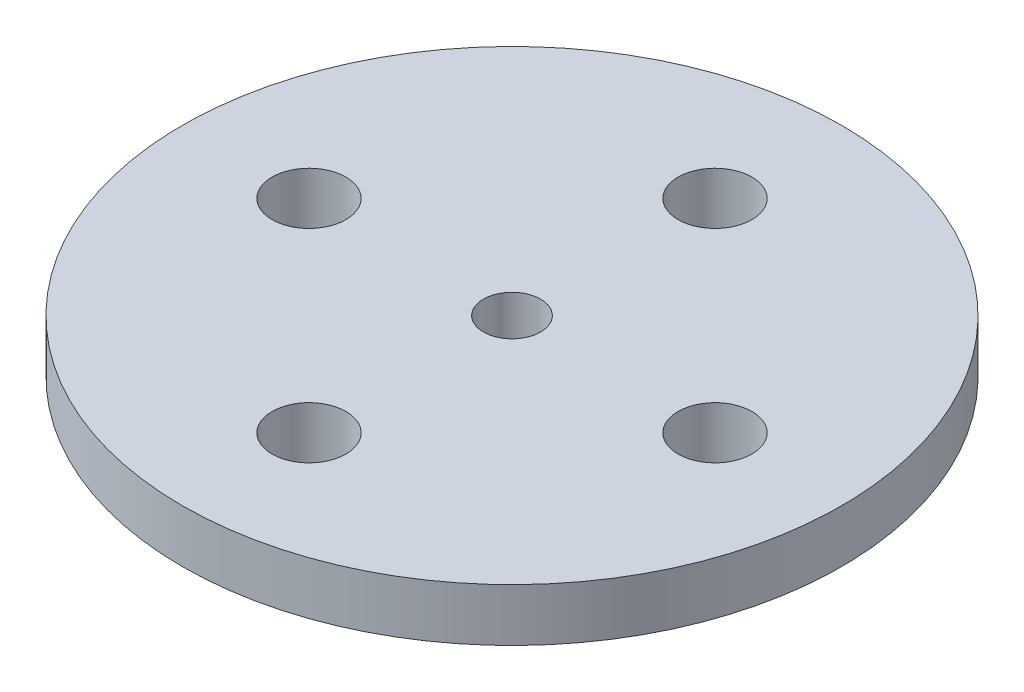
SolidWorks part; units mm, degrees
ref_plane "Front Plane" through (0, 0, 0) normal (0, 0, 1) x (1, 0, 0)
ref_plane "Top Plane" through (0, 0, 0) normal (0, 1, 0) x (1, 0, 0)
ref_plane "Right Plane" through (0, 0, 0) normal (1, 0, 0) x (0, 0, -1)
sketch "Sketch1" plane through (0, 0, 0) normal (0, 1, 0) x (1, 0, 0)
  line L0 (0, 15.5) -> (0, -15.5) construction
  line L1 (-15.5, 0) -> (15.5, 0) construction
  line L2 (-2.4674, 13.4022) -> (-4, 4) construction
  line L3 (4, -4) -> (-4, -4) construction
  line L4 (4, -4) -> (4, 4) construction
  line L5 (4, 4) -> (-4, 4) construction
  line L6 (-4, -4) -> (-4, 4) construction
  line L7 (4, -4) -> (-4, 4) construction
  line L8 (4, 4) -> (-4, -4) construction
  line L9 (-4, 4) -> (-2.4674, 13.4022)
  line L10 (4, 4) -> (2.4674, 13.4022)
  line L11 (4, -4) -> (2.4674, -13.4022)
  line L12 (-4, -4) -> (-2.4674, -13.4022)
  line L13 (-4, 4) -> (-12.5927, 2.4331) construction
  line L14 (-4, 4) -> (-12.4485, 2.4594)
  line L15 (-4, -4) -> (-12.4485, -2.4594)
  line L16 (4, -4) -> (12.4485, -2.4594)
  line L17 (4, 4) -> (12.4485, 2.4594)
  circle A0 centre (0, 0) radius 15.5 construction
  circle A1 centre (0, 0) radius 14.5 construction
  arc A2 (2.4674, 13.4022) -> (-2.4674, 13.4022) centre (0, 13) ccw
  arc A3 (2.4674, -13.4022) -> (-2.4674, -13.4022) centre (0, -13) cw
  arc A4 (-12.4485, 2.4594) -> (-12.4485, -2.4594) centre (-12, 0) ccw
  arc A5 (12.4485, 2.4594) -> (12.4485, -2.4594) centre (12, 0) cw
  circle A6 centre (0, 0) radius 12 construction
  circle A7 centre (0, 0) radius 9.5 construction
  circle A8 centre (0, 0) radius 7.5 construction
  circle A9 centre (0, 12) radius 0.5
  circle A10 centre (0, 9.5) radius 0.5
  circle A11 centre (0, 7.5) radius 0.5
  circle A12 centre (12, 0) radius 0.5
  circle A13 centre (9.5, 0) radius 0.5
  circle A14 centre (7.5, 0) radius 0.5
  circle A15 centre (0, -12) radius 0.5
  circle A16 centre (0, -9.5) radius 0.5
  circle A17 centre (0, -7.5) radius 0.5
  circle A18 centre (-12, 0) radius 0.5
  circle A19 centre (-9.5, 0) radius 0.5
  circle A20 centre (-7.5, 0) radius 0.5
  circle A21 centre (0, 0) radius 1.375
  point P59 (0, 0)
  dimension "D1" = 31
  dimension "D2" = 1
  dimension "D3" = 5
  dimension "D4" = 5
  dimension "D5" = 8
  dimension "D6" = 8
  dimension "D7" = 15
  dimension "D9" = 24
  dimension "D11" = 1
  dimension "D12" = 1
  dimension "D13" = 4
  dimension "D8" = 19
  dimension "D10" = 1
  dimension "D14" = 2.75
extrude "Boss-Extrude1" add sketch "Sketch1" along normal blind 2
sketch "Sketch4" plane through (0, 0, 0) normal (0, -1, 0) x (1, 0, 0)
  circle A0 centre (0, 0) radius 4.5
  circle A1 centre (0, 0) radius 2.5
  dimension "D1" = 9
  dimension "D2" = 2
extrude "Boss-Extrude3" add sketch "Sketch4" along normal blind 2.5
sketch "Sketch5" plane through (0, -2.5, 0) normal (0, -1, 0) x (1, 0, 0)
  line L0 (0, 0) -> (0, 0.6245) construction
  line L1 (0, 3) -> (-0.299, 2.4821)
  line L2 (0, 3) -> (0.299, 2.4821)
  line L3 (0.9271, 2.8532) -> (0.4826, 2.453)
  line L4 (0.9271, 2.8532) -> (1.0514, 2.2682)
  line L5 (1.7634, 2.4271) -> (1.217, 2.1838)
  line L6 (1.7634, 2.4271) -> (1.7008, 1.8323)
  line L7 (2.4271, 1.7634) -> (1.8323, 1.7008)
  line L8 (2.4271, 1.7634) -> (2.1838, 1.217)
  line L9 (2.8532, 0.9271) -> (2.2682, 1.0514)
  line L10 (2.8532, 0.9271) -> (2.453, 0.4826)
  line L11 (3, 0) -> (2.4821, 0.299)
  line L12 (3, 0) -> (2.4821, -0.299)
  line L13 (2.8532, -0.9271) -> (2.453, -0.4826)
  line L14 (2.8532, -0.9271) -> (2.2682, -1.0514)
  line L15 (2.4271, -1.7634) -> (2.1838, -1.217)
  line L16 (2.4271, -1.7634) -> (1.8323, -1.7008)
  line L17 (1.7634, -2.4271) -> (1.7008, -1.8323)
  line L18 (1.7634, -2.4271) -> (1.217, -2.1838)
  line L19 (0.9271, -2.8532) -> (1.0514, -2.2682)
  line L20 (0.9271, -2.8532) -> (0.4826, -2.453)
  line L21 (0, -3) -> (0.299, -2.4821)
  line L22 (0, -3) -> (-0.299, -2.4821)
  line L23 (-0.9271, -2.8532) -> (-0.4826, -2.453)
  line L24 (-0.9271, -2.8532) -> (-1.0514, -2.2682)
  line L25 (-1.7634, -2.4271) -> (-1.217, -2.1838)
  line L26 (-1.7634, -2.4271) -> (-1.7008, -1.8323)
  line L27 (-2.4271, -1.7634) -> (-1.8323, -1.7008)
  line L28 (-2.4271, -1.7634) -> (-2.1838, -1.217)
  line L29 (-2.8532, -0.9271) -> (-2.2682, -1.0514)
  line L30 (-2.8532, -0.9271) -> (-2.453, -0.4826)
  line L31 (-3, 0) -> (-2.4821, -0.299)
  line L32 (-3, 0) -> (-2.4821, 0.299)
  line L33 (-2.8532, 0.9271) -> (-2.453, 0.4826)
  line L34 (-2.8532, 0.9271) -> (-2.2682, 1.0514)
  line L35 (-2.4271, 1.7634) -> (-2.1838, 1.217)
  line L36 (-2.4271, 1.7634) -> (-1.8323, 1.7008)
  line L37 (-1.7634, 2.4271) -> (-1.7008, 1.8323)
  line L38 (-1.7634, 2.4271) -> (-1.217, 2.1838)
  line L39 (-0.9271, 2.8532) -> (-1.0514, 2.2682)
  line L40 (-0.9271, 2.8532) -> (-0.4826, 2.453)
  circle A0 centre (0, 0) radius 2.5 construction
  arc A1 (-2.1838, 1.217) -> (-2.2682, 1.0514) centre (0, 0) ccw
  arc A2 (-1.7008, 1.8323) -> (-1.8323, 1.7008) centre (0, 0) ccw
  arc A3 (-1.0514, 2.2682) -> (-1.217, 2.1838) centre (0, 0) ccw
  arc A4 (-0.299, 2.4821) -> (-0.4826, 2.453) centre (0, 0) ccw
  arc A5 (0.4826, 2.453) -> (0.299, 2.4821) centre (0, 0) ccw
  arc A6 (1.217, 2.1838) -> (1.0514, 2.2682) centre (0, 0) ccw
  arc A7 (1.8323, 1.7008) -> (1.7008, 1.8323) centre (0, 0) ccw
  arc A8 (2.2682, 1.0514) -> (2.1838, 1.217) centre (0, 0) ccw
  arc A9 (2.4821, 0.299) -> (2.453, 0.4826) centre (0, 0) ccw
  arc A10 (2.453, -0.4826) -> (2.4821, -0.299) centre (0, 0) ccw
  arc A11 (2.1838, -1.217) -> (2.2682, -1.0514) centre (0, 0) ccw
  arc A12 (1.7008, -1.8323) -> (1.8323, -1.7008) centre (0, 0) ccw
  arc A13 (1.0514, -2.2682) -> (1.217, -2.1838) centre (0, 0) ccw
  arc A14 (0.299, -2.4821) -> (0.4826, -2.453) centre (0, 0) ccw
  arc A15 (-0.4826, -2.453) -> (0, -2.5) centre (0, 0) ccw
  arc A16 (-1.217, -2.1838) -> (-1.0514, -2.2682) centre (0, 0) ccw
  arc A17 (-1.8323, -1.7008) -> (-1.7008, -1.8323) centre (0, 0) ccw
  arc A18 (-2.2682, -1.0514) -> (-2.1838, -1.217) centre (0, 0) ccw
  arc A19 (-2.4821, -0.299) -> (-2.453, -0.4826) centre (0, 0) ccw
  arc A20 (-2.453, 0.4826) -> (-2.4821, 0.299) centre (0, 0) ccw
  point P68 (0, 0)
  circle M5 centre (0, 0) radius 2.5
  dimension "D1" = 30
  dimension "D2" = 3
  dimension "D3" = 20
extrude "Cut-Extrude3" cut sketch "Sketch5" against normal up to surface (2.5 mm away) contours L36 L35 M5 | L34 L33 M5 | L32 L31 M5 | L30 L29 M5 | L28 L27 M5 | L26 L25 M5 | L24 L23 M5 | L0 L21 M5 | L22 L0 M5 | L20 L19 M5 | L18 L17 M5 | L16 L15 M5 | L14 L13 M5 | L12 L11 M5 | L10 L9 M5 | L8 L7 M5 | L6 L5 M5 | L4 L3 M5 | L0 L2 M5 | L0 L1 M5 | L40 L39 M5 | L38 L37 M5 region at (0, -2.5, 2.6627) region at (-0.8228, -2.5, 2.5324) region at (0.8228, -2.5, 2.5324) region at (-1.5651, -2.5, 2.1542) region at (1.5651, -2.5, 2.1542) region at (-2.1542, -2.5, 1.5651) region at (2.1542, -2.5, 1.5651) region at (-2.5324, -2.5, 0.8228) region at (2.5324, -2.5, 0.8228) region at (-2.6627, -2.5, 0) region at (2.6627, -2.5, 0) region at (-2.5324, -2.5, -0.8228) region at (2.5324, -2.5, -0.8228) region at (-2.1542, -2.5, -1.5651) region at (2.1542, -2.5, -1.5651) region at (-1.5651, -2.5, -2.1542) region at (1.5651, -2.5, -2.1542) region at (-0.8228, -2.5, -2.5324) region at (0.8228, -2.5, -2.5324) region at (0, -2.5, -2.6627) up to face at (0, 0, 1.375)
sketch "Sketch6" plane through (0, 2, 0) normal (0, 1, 0) x (1, 0, 0)
  circle A0 centre (0, 0) radius 15.875
  circle A2 centre (0, 0) radius 3.75
  dimension "D1" = 31.75
extrude "Boss-Extrude6" add sketch "Sketch6" against normal blind 2.54
sketch "Sketch7" plane through (0, 2, 0) normal (0, 1, 0) x (1, 0, 0)
  circle A0 centre (0, 9.779) radius 1.778
extrude "Cut-Extrude4" cut sketch "Sketch7" against normal blind 2.54
pattern_circular "CirPattern1" count 4 over 360 about axis through (0, 2, 0) along (0, -1, 0) of "Cut-Extrude4"
